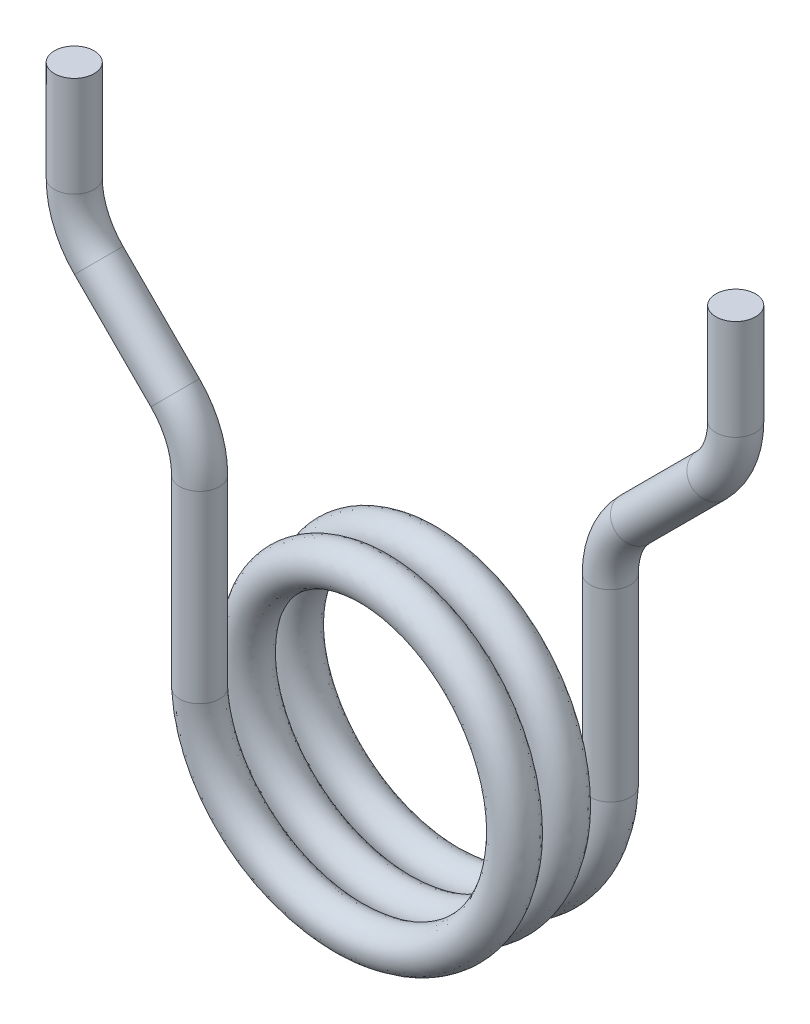
SolidWorks part; units mm, degrees
note: '?' marks a value the reader was unsure of. The reader was unsure of these and kept them because the rebuilt part matched: shared geometry of "Esboço2<7>".
material "Ouro puro"
ref_plane "Plano frontal" through (0, 0, 0) normal (0, 0, 1) x (1, 0, 0)
ref_plane "Plano superior" through (0, 0, 0) normal (0, 1, 0) x (1, 0, 0)
ref_plane "Plano direito" through (0, 0, 0) normal (1, 0, 0) x (0, 0, -1)
sketch "Esboço1" plane through (0, 0, 0) normal (0, 0, 1) x (1, 0, 0)
  circle A0 centre (0, 0) radius 17.375
  dimension "D1" = 34.75
curve "Hélice/Espiral2" pitch 5.75 height 14.375 turns 2.5
sketch "Esboço2" plane through (0, 0, 0) normal (0, 1, 0) x (1, 0, 0)
  circle A0 centre (17.375, 0) radius 2.375
  spline S0 degree 3 poles (17.375, 0) (17.375, -0.1037) (16.6931, -0.3127) (13.7425, -0.6249) (9.2049, -0.9375) (3.6044, -1.25) (-2.4123, -1.5625) (-8.1505, -1.875) (-12.9475, -2.1875) (-16.2493, -2.5) (-17.6747, -2.8125) (-17.059, -3.125) (-14.4734, -3.4375) (-10.2165, -3.75) (-4.7797, -4.0625) (1.209, -4.375) (7.0581, -4.6875) (12.0921, -5) (15.7297, -5.3125) (17.551, -5.625) (17.3454, -5.9375) (15.1369, -6.25) (11.1803, -6.5625) (5.9327, -6.875) (0, -7.1875) (-5.9327, -7.5) (-11.1803, -7.8125) (-15.1369, -8.125) (-17.3454, -8.4375) (-17.551, -8.75) (-15.7297, -9.0625) (-12.0921, -9.375) (-7.0581, -9.6875) (-1.209, -10) (4.7797, -10.3125) (10.2165, -10.625) (14.4734, -10.9375) (17.059, -11.25) (17.6747, -11.5625) (16.2493, -11.875) (12.9475, -12.1875) (8.1505, -12.5) (2.4123, -12.8125) (-3.6044, -13.125) (-9.2049, -13.4375) (-13.7425, -13.7501) (-16.6931, -14.0623) (-17.375, -14.2713) (-17.375, -14.375) knots 0 0 0 0 0.021739 0.043478 0.065217 0.086957 0.108696 0.130435 0.152174 0.173913 0.195652 0.217391 0.23913 0.26087 0.282609 0.304348 0.326087 0.347826 0.369565 0.391304 0.413043 0.434783 0.456522 0.478261 0.5 0.521739 0.543478 0.565217 0.586957 0.608696 0.630435 0.652174 0.673913 0.695652 0.717391 0.73913 0.76087 0.782609 0.804348 0.826087 0.847826 0.869565 0.891304 0.913043 0.934783 0.956522 0.978261 1 1 1 1 construction
  dimension "D1" = 4.75
sweep "Varredura1" add profiles "Esboço2" path "Hélice/Espiral2"
ref_point "Ponto1"
sketch "Esboço3" plane through (0, 0, 0) normal (0, 1, 0) x (1, 0, 0)
  circle A0 centre (-17.375, -14.375) radius 2.375
  dimension "D1" = 4.75
ref_axis "Eixo1" through (0, 0, -25.837) along (0, 0, 1)?
ref_plane "Plano1" through (0, 0, 14.375) normal (0, 0, 1) x (1, 0, 0)
sketch "Esboço5" plane through (0, 0, 14.375) normal (0, 0, 1) x (1, 0, 0)
  line L0 (-17.375, 0) -> (-17.375, 22)
  line L1 (-15, 0) -> (-19.75, 0) construction
  line L2 (-20.3039, 29.0711) -> (-29.4461, 38.2132)
  line L3 (-32.375, 45.2843) -> (-32.375, 57.2843)
  line L4 (-20.3039, 29.0711) -> (-39.611, 29.0711) construction
  arc A0 (-32.375, 45.2843) -> (-29.4461, 38.2132) centre (-22.375, 45.2843) ccw
  arc A1 (-20.3039, 29.0711) -> (-17.375, 22) centre (-27.375, 22) cw
  dimension "D1" = 10
  dimension "D2" = 22
  dimension "D3" = 12
  dimension "D4" = 15
  dimension "D5" = 45
sketch "Esboço8" plane through (0, 0, 0) normal (0, 0, 1) x (1, 0, 0)
  line L0 (17.375, 0) -> (17.375, 22)
  line L1 (19.75, 0) -> (15, 0) construction
  line L2 (20.3039, 29.0711) -> (29.4461, 38.2132)
  line L3 (32.375, 45.2843) -> (32.375, 57.2843)
  line L4 (20.3039, 29.0711) -> (38.184, 29.0711) construction
  arc A0 (32.375, 45.2843) -> (29.4461, 38.2132) centre (22.375, 45.2843) cw
  arc A1 (20.3039, 29.0711) -> (17.375, 22) centre (27.375, 22) ccw
  dimension "D1" = 10
  dimension "D2" = 22
  dimension "D3" = 45
  dimension "D4" = 15
  dimension "D5" = 12
sweep "Varredura2" add profiles "Esboço2<7>" path "Esboço8"
sketch "Esboço2<7>" plane through (0, 0, 0) normal (0, 1, 0) x (1, 0, 0) same geometry as "Esboço2"
sweep "Varredura3" add profiles "Esboço3" path "Esboço5"
ref_plane "WorkPlane" through (0, 0, 7.1875) normal (0, 0, 1) x (1, 0, 0)
equation "\"diam_interno\"=30"
equation "\"diam_tubo\"=4.75"
equation "\"D1@Esboço2\"=\"diam_tubo\""
equation "\"turn_gap\"=1"
equation "\"turn_step\"=((\"diam_tubo\"/2)+(\"turn_gap\"/2))*2"
equation "\"coil_height\"=\"turn_step\"*2.5"
equation "\"D4@Hélice/Espiral2\"=\"turn_step\""
equation "\"D3@Hélice/Espiral2\"=\"coil_height\""
equation "\"D1@Esboço1\" = \"diam_interno\"+\"diam_tubo\""
equation "\"D1@Esboço3\"=\"diam_tubo\""
equation "\"coil_arm\"=90"
